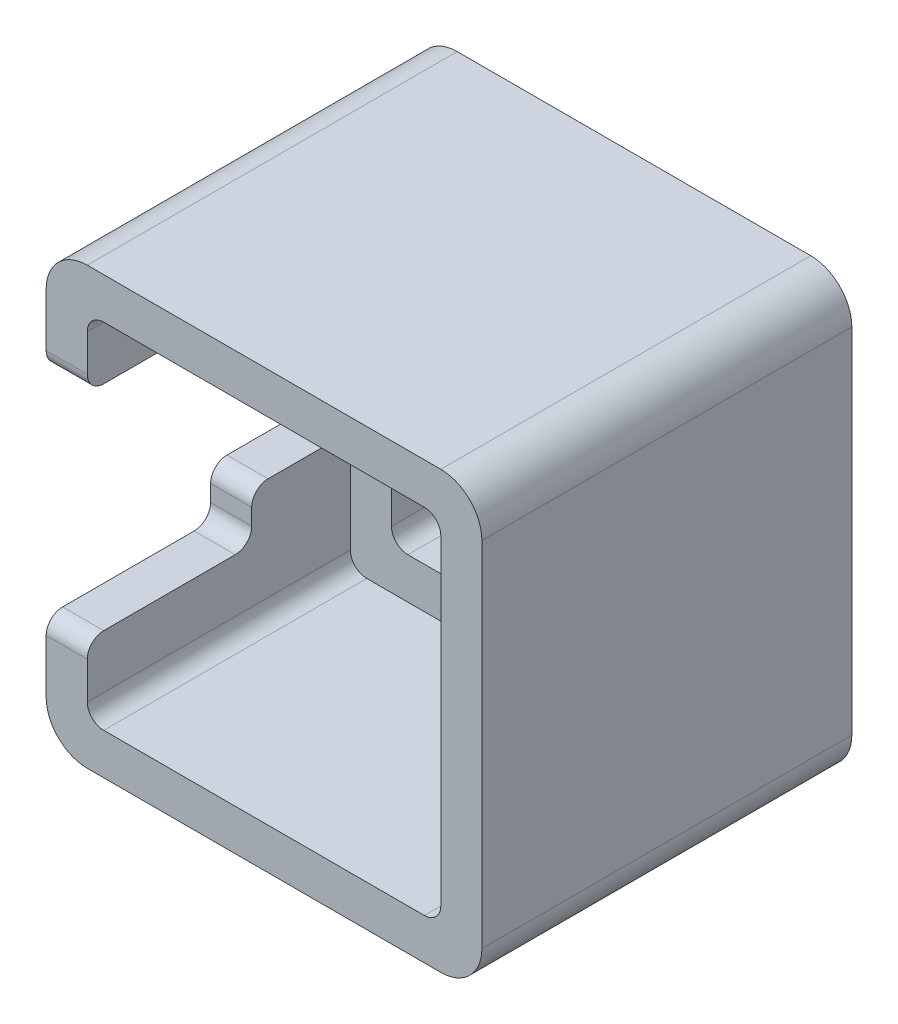
SolidWorks part; units mm, degrees
ref_plane "Alzado" through (0, 0, 0) normal (1, 0, 0) x (0, 1, 0)
ref_plane "Planta" through (0, 0, 0) normal (0, 0, 1) x (0, 1, 0)
ref_plane "Vista lateral" through (0, 0, 0) normal (0, 1, 0) x (-1, 0, 0)
sketch "Croquis1" plane through (0, 0, 0) normal (0, 0, 1) x (0, 1, 0)
  line L0 (-26.5, 0) -> (26.5, 0) construction
  line L1 (-21.5, -21.5) -> (21.5, -21.5) construction
  line L2 (-21.5, -21.5) -> (-21.5, 21.5) construction
  line L3 (-21.5, 21.5) -> (21.5, 21.5) construction
  line L4 (21.5, -21.5) -> (21.5, 21.5) construction
  line L5 (-21.5, -21.5) -> (21.5, 21.5) construction
  line L6 (-21.5, 21.5) -> (21.5, -21.5) construction
  line L7 (-21.5, 21.5) -> (-26.5, 21.5)
  line L8 (-21.5, 21.5) -> (-21.5, -21.5)
  line L9 (-21.5, -21.5) -> (-26.5, -21.5)
  line L10 (-26.5, 21.5) -> (-26.5, -21.5)
  line L11 (21.5, 21.5) -> (26.5, 21.5)
  line L12 (21.5, 21.5) -> (21.5, -21.5)
  line L13 (21.5, -21.5) -> (26.5, -21.5)
  line L14 (26.5, 21.5) -> (26.5, -21.5)
  line L15 (-21.5, 21.5) -> (-26.5, 21.5)
  line L16 (-21.5, 21.5) -> (-21.5, 26.5)
  line L17 (-21.5, 26.5) -> (-26.5, 26.5)
  line L18 (-26.5, 21.5) -> (-26.5, 26.5)
  line L19 (26.5, 21.5) -> (21.5, 21.5)
  line L20 (26.5, 21.5) -> (26.5, 26.5)
  line L21 (26.5, 26.5) -> (21.5, 26.5)
  line L22 (21.5, 21.5) -> (21.5, 26.5)
  line L23 (26.5, -26.5) -> (21.5, -26.5)
  line L24 (21.5, -21.5) -> (21.5, -26.5)
  line L25 (26.5, -21.5) -> (21.5, -21.5)
  line L26 (26.5, -21.5) -> (26.5, -26.5)
  line L27 (-21.5, -26.5) -> (-26.5, -26.5)
  line L28 (-26.5, -21.5) -> (-26.5, -26.5)
  line L29 (-21.5, -21.5) -> (-26.5, -21.5)
  line L30 (-21.5, -21.5) -> (-21.5, -26.5)
  point P0 (0, 0)
  dimension "D1" = 43
  dimension "D2" = 43
  dimension "D3" = 5
  dimension "D4" = 5
  dimension "D5" = 5
  dimension "D6" = 5
extrude "Saliente-Extruir1" add sketch "Croquis1" along normal blind 3 contours L30 L9 L28 L27 | L26 L13 L24 L23 | L8 L7 L10 L9 | L16 L15 L18 L17 | L20 L19 L22 L21 | L12 L11 L14 L13 region at (24, -24, 0) region at (24, 24, 0)
sketch "Croquis3" plane through (0, 0, 3) normal (0, 0, 1) x (1, 0, 0)
  line L1 (-26.5, -26.5) -> (-26.5, 26.5)
  line L3 (-26.5, 26.5) -> (26.5, 26.5)
  line L4 (-26.5, 26.5) -> (26.5, 26.5) construction
  line L10 (26.5, -26.5) -> (-26.5, -26.5) construction
  line L11 (16.5, 16.5) -> (-16.5, 16.5)
  line L12 (16.5, 16.5) -> (16.5, -16.5)
  line L13 (16.5, -16.5) -> (-16.5, -16.5)
  line L14 (-16.5, 16.5) -> (-16.5, -16.5)
  line L15 (16.5, 16.5) -> (-16.5, -16.5) construction
  line L16 (16.5, -16.5) -> (-16.5, 16.5) construction
  line L17 (-26.5, -26.5) -> (26.5, -26.5)
  line L20 (26.5, -26.5) -> (26.5, 26.5)
  line L22 (-26.5, -21.5) -> (-26.5, -26.5) construction
  point P0 (0, 0)
  point P14 (0, 0)
  line M33 (26.5, -26.5) -> (26.5, -21.5)
  line M34 (26.5, -21.5) -> (-26.5, -21.5)
  line M35 (-26.5, -21.5) -> (-26.5, -26.5)
  line M36 (-26.5, -26.5) -> (26.5, -26.5)
  dimension "D1" = 10
  dimension "D2" = 10
  dimension "D3" = 10
extrude "Saliente-Extruir2" add sketch "Croquis3" along normal blind 10 contours L20 L3 L1 L14 L11 L12 L13 M34 | M36 M33 M34 M35 region at (0, -24, 3) region at (-25.7849, 2.5, 3)
sketch "Croquis4" plane through (0, 0, 13) normal (0, 0, 1) x (1, 0, 0)
  line L1 (-26.5, -26.5) -> (26.5, -26.5)
  line L2 (-26.5, -26.5) -> (-26.5, 26.5)
  line L3 (-26.5, 26.5) -> (26.5, 26.5)
  line L4 (26.5, -26.5) -> (26.5, 26.5)
  line L5 (-21.5, -21.5) -> (21.5, -21.5)
  line L6 (-21.5, -21.5) -> (-21.5, 21.5)
  line L7 (-21.5, 21.5) -> (21.5, 21.5)
  line L8 (21.5, -21.5) -> (21.5, 21.5)
  line L9 (-21.5, -21.5) -> (21.5, 21.5) construction
  line L10 (-21.5, 21.5) -> (21.5, -21.5) construction
  point P6 (0, 0)
  dimension "D1" = 5
  dimension "D2" = 5
extrude "Saliente-Extruir3" add sketch "Croquis4" along normal blind 32
fillet "Redondeo1" radius 2 4 edges at (21.5, -21.5, 29) (21.5, 21.5, 29) (-21.5, 21.5, 29) (-21.5, -21.5, 29)
fillet "Redondeo2" radius 5 4 edges at (-26.5, 26.5, 22.5) (26.5, 26.5, 22.5) (26.5, -26.5, 22.5) (-26.5, -26.5, 22.5)
sketch "Croquis5" plane through (0, 0, 45) normal (0, 0, 1) x (1, 0, 0)
  line L0 (-26.5, 21.5) -> (-26.5, -21.5) construction
  line L1 (-26.5, -7) -> (-21.5, -7)
  line L2 (-26.5, -7) -> (-26.5, 7)
  line L3 (-26.5, 7) -> (-21.5, 7)
  line L4 (-21.5, -7) -> (-21.5, 7)
  line L5 (-21.5, 19.5) -> (-21.5, -19.5) construction
  point P8 (-21.5, 0)
  dimension "D1" = 14
extrude "Cortar-Extruir1" cut sketch "Croquis5" against normal up to surface (32 mm away) up to face at (0, 0, 13)
sketch "Croquis6" plane through (0, 0, 45) normal (0, 0, 1) x (1, 0, 0)
  line L1 (-26.5, 7) -> (-21.5, 7)
  line L2 (-26.5, 7) -> (-26.5, 13)
  line L3 (-26.5, 13) -> (-21.5, 13)
  line L4 (-21.5, 7) -> (-21.5, 13)
  line L5 (-21.5, -7) -> (-21.5, -19.5) construction
  line L6 (-26.5, -7) -> (-21.5, -7)
  line L7 (-26.5, -7) -> (-26.5, -13)
  line L8 (-26.5, -13) -> (-21.5, -13)
  line L9 (-21.5, -7) -> (-21.5, -13)
  line L10 (-26.5, 21.5) -> (-26.5, 7) construction
  dimension "D1" = 6
  dimension "D2" = 6
  dimension "D3" = 5
extrude "Cortar-Extruir2" cut sketch "Croquis6" against normal blind 20 contours L7 L6 L9 L8 | L2 L1 L4 L3
fillet "Redondeo3" radius 2 8 edges at (-24, -7, 13) (-24, 7, 13) (-24, -13, 45) (-24, -13, 25) (-24, -7, 25) (-24, 7, 25) (-24, 13, 25) (-24, 13, 45)
sketch "Croquis7" plane through (0, 0, 0) normal (0, 0, 1) x (0, 1, 0)
  line L5 (0, 0) -> (-21.5, 0) construction
  line L6 (-21.5, 19.5) -> (-21.5, -19.5) construction
  line L7 (0, 16.5) -> (0, -16.5) construction
  line L8 (16.5, 16.5) -> (-16.5, 16.5) construction
  line L9 (16.5, -16.5) -> (-16.5, -16.5) construction
  line L10 (-21.5, -7.5) -> (-21.5, 7.5)
  line L11 (-21.5, 7.5) -> (-9.3437, 3.8292)
  line L12 (-21.5, -7.5) -> (-9.3437, -3.8292)
  circle A0 centre (-10.5, 0) radius 1.75
  circle A1 centre (-10.5, 0) radius 4
  point P14 (-21.5, 0)
  dimension "D1" = 3.5
  dimension "D4" = 2.25
  dimension "D2" = 11
  dimension "D3" = 15
extrude "Saliente-Extruir4" add sketch "Croquis7" along normal blind 3 contours A1 L11 L10 L12 | A1 A0 region at (0, -17.5632, 0) region at (0, -14.3869, 0)
fillet "Redondeo4" radius 3 2 edges at (-7.5, -21.5, 1.5) (7.5, -21.5, 1.5)
mirror "Simetría5" about plane through (0, 0, 0) normal (0, 1, 0) of "Saliente-Extruir4"
fillet "Redondeo7" radius 3 2 edges at (7.5, 21.5, 1.5) (-7.5, 21.5, 1.5)
sketch "Croquis9" plane through (0, 0, 3) normal (0, 0, -1) x (1, 0, 0)
  line L16 (-26.5, -21.5) -> (-9.7279, -21.5)
  line L17 (-6.856, -19.3672) -> (-5.9902, -16.5)
  line L18 (-5.9902, -16.5) -> (-16.5, -16.5)
  line L19 (-16.5, -16.5) -> (-16.5, 16.5)
  line L20 (-16.5, 16.5) -> (-5.9902, 16.5)
  line L21 (-5.9902, 16.5) -> (-6.856, 19.3672)
  line L22 (-9.7279, 21.5) -> (-26.5, 21.5)
  line L23 (-26.5, 21.5) -> (-26.5, -21.5)
  line L24 (-26.5, -21.5) -> (-9.7279, -21.5)
  line L25 (-6.856, -19.3672) -> (-5.9902, -16.5)
  line L26 (-5.9902, -16.5) -> (-16.5, -16.5)
  line L27 (-16.5, -16.5) -> (-16.5, 16.5)
  line L28 (-16.5, 16.5) -> (-5.9902, 16.5)
  line L29 (-5.9902, 16.5) -> (-6.856, 19.3672)
  line L30 (-9.7279, 21.5) -> (-26.5, 21.5)
  line L31 (-26.5, 21.5) -> (-26.5, -21.5)
  line L40 (5.9902, -16.5) -> (6.856, -19.3672)
  line L41 (9.7279, -21.5) -> (26.5, -21.5)
  line L42 (26.5, -21.5) -> (26.5, 21.5)
  line L43 (26.5, 21.5) -> (9.7279, 21.5)
  line L44 (6.856, 19.3672) -> (5.9902, 16.5)
  line L45 (5.9902, 16.5) -> (16.5, 16.5)
  line L46 (16.5, 16.5) -> (16.5, -16.5)
  line L47 (16.5, -16.5) -> (5.9902, -16.5)
  line L48 (5.9902, -16.5) -> (6.856, -19.3672)
  line L49 (9.7279, -21.5) -> (26.5, -21.5)
  line L50 (26.5, -21.5) -> (26.5, 21.5)
  line L51 (26.5, 21.5) -> (9.7279, 21.5)
  line L52 (6.856, 19.3672) -> (5.9902, 16.5)
  line L53 (5.9902, 16.5) -> (16.5, 16.5)
  line L54 (16.5, 16.5) -> (16.5, -16.5)
  line L55 (16.5, -16.5) -> (5.9902, -16.5)
  arc A4 (-9.7279, -21.5) -> (-6.856, -19.3672) centre (-9.7279, -18.5) ccw
  arc A5 (-6.856, 19.3672) -> (-9.7279, 21.5) centre (-9.7279, 18.5) ccw
  arc A6 (-9.7279, -21.5) -> (-6.856, -19.3672) centre (-9.7279, -18.5) ccw
  arc A7 (-6.856, 19.3672) -> (-9.7279, 21.5) centre (-9.7279, 18.5) ccw
  arc A10 (6.856, -19.3672) -> (9.7279, -21.5) centre (9.7279, -18.5) ccw
  arc A11 (9.7279, 21.5) -> (6.856, 19.3672) centre (9.7279, 18.5) ccw
  arc A12 (6.856, -19.3672) -> (9.7279, -21.5) centre (9.7279, -18.5) ccw
  arc A13 (9.7279, 21.5) -> (6.856, 19.3672) centre (9.7279, 18.5) ccw
  dimension "D1" = 0
  dimension "D2" = 0
extrude "Saliente-Extruir5" add sketch "Croquis9" along normal blind 3
fillet "Redondeo8" radius 2 8 edges at (5.9902, 16.5, 1.5) (-5.9902, 16.5, 1.5) (-5.9902, -16.5, 1.5) (5.9902, -16.5, 1.5) (16.5, -16.5, 6.5) (-16.5, -16.5, 6.5) (-16.5, 16.5, 6.5) (16.5, 16.5, 6.5)
